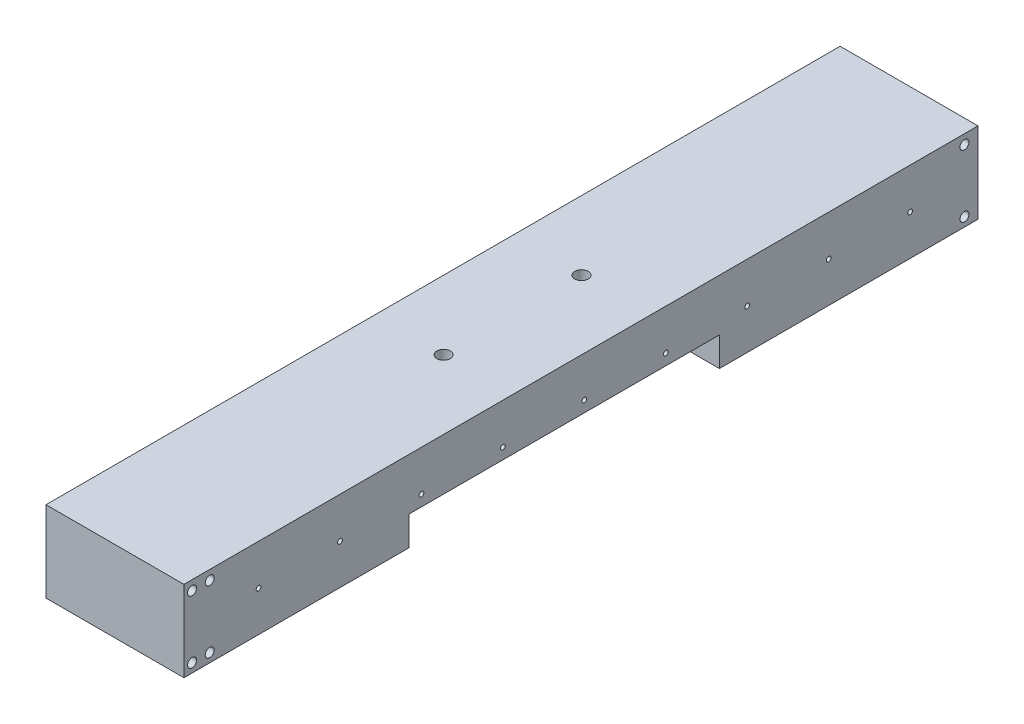
SolidWorks part; units mm, degrees
ref_plane "Front" through (0, 0, 0) normal (0, 0, 1) x (1, 0, 0)
ref_plane "Top" through (0, 0, 0) normal (0, 1, 0) x (1, 0, 0)
ref_plane "Right" through (0, 0, 0) normal (1, 0, 0) x (0, 0, -1)
sketch "Sketch1" plane through (0, 0, 0) normal (0, 0, 1) x (1, 0, 0)
  line L1 (0, 0) -> (101.6, 0)
  line L2 (0, 0) -> (0, 59.6)
  line L3 (0, 59.6) -> (101.6, 59.6)
  line L4 (101.6, 0) -> (101.6, 59.6)
  dimension "D1" = 59.6
  dimension "D2" = 101.6
extrude "Boss-Extrude1" add sketch "Sketch1" along normal blind 585.0001
sketch "Sketch2" plane through (0, 0, 0) normal (-1, 0, 0) x (0, 0, 1)
  line L0 (190.5, 0) -> (190.5, 21.5)
  line L1 (585.0001, 0) -> (0, 0) construction
  line L2 (190.5, 21.5) -> (419.1, 21.5)
  line L3 (419.1, 21.5) -> (419.1, 0)
  line L4 (419.1, 0) -> (190.5, 0)
  line L5 (0, 59.6) -> (0, 0) construction
  dimension "D1" = 190.5
  dimension "D2" = 21.5
  dimension "D3" = 228.6
extrude "Cut-Extrude1" cut sketch "Sketch2" against normal through all
sketch "Sketch5" plane through (0, 0, 0) normal (-1, 0, 0) x (0, 0, 1)
  arc A0 (6.7, 6.6) -> (13.3, 6.6) centre (10, 6.6) ccw construction
  arc A1 (13.3, 6.6) -> (6.7, 6.6) centre (10, 6.6) ccw construction
  arc A2 (6.7, 52.6) -> (13.3, 52.6) centre (10, 52.6) ccw construction
  arc A3 (13.3, 52.6) -> (6.7, 52.6) centre (10, 52.6) ccw construction
  arc A4 (6.7, 6.6) -> (13.3, 6.6) centre (10, 6.6) ccw
  arc A5 (13.3, 6.6) -> (6.7, 6.6) centre (10, 6.6) ccw
  arc A6 (6.7, 52.6) -> (13.3, 52.6) centre (10, 52.6) ccw
  arc A7 (13.3, 52.6) -> (6.7, 52.6) centre (10, 52.6) ccw
  arc A8 (170, 31.35) -> (170, 27.85) centre (170, 29.6) ccw construction
  arc A9 (170, 27.85) -> (170, 31.35) centre (170, 29.6) ccw construction
  arc A10 (110, 27.85) -> (110, 31.35) centre (110, 29.6) ccw construction
  arc A11 (110, 31.35) -> (110, 27.85) centre (110, 29.6) ccw construction
  arc A12 (50, 27.85) -> (50, 31.35) centre (50, 29.6) ccw construction
  arc A13 (50, 31.35) -> (50, 27.85) centre (50, 29.6) ccw construction
  arc A14 (170, 31.35) -> (170, 27.85) centre (170, 29.6) ccw
  arc A15 (170, 27.85) -> (170, 31.35) centre (170, 29.6) ccw
  arc A16 (110, 27.85) -> (110, 31.35) centre (110, 29.6) ccw
  arc A17 (110, 31.35) -> (110, 27.85) centre (110, 29.6) ccw
  arc A18 (50, 27.85) -> (50, 31.35) centre (50, 29.6) ccw
  arc A19 (50, 31.35) -> (50, 27.85) centre (50, 29.6) ccw
  arc A20 (530, 27.85) -> (530, 31.35) centre (530, 29.6) ccw construction
  arc A21 (530, 31.35) -> (530, 27.85) centre (530, 29.6) ccw construction
  arc A22 (470, 27.85) -> (470, 31.35) centre (470, 29.6) ccw construction
  arc A23 (470, 31.35) -> (470, 27.85) centre (470, 29.6) ccw construction
  arc A24 (410, 27.85) -> (410, 31.35) centre (410, 29.6) ccw construction
  arc A25 (410, 31.35) -> (410, 27.85) centre (410, 29.6) ccw construction
  arc A26 (350, 27.85) -> (350, 31.35) centre (350, 29.6) ccw construction
  arc A27 (350, 31.35) -> (350, 27.85) centre (350, 29.6) ccw construction
  arc A28 (290, 27.85) -> (290, 31.35) centre (290, 29.6) ccw construction
  arc A29 (290, 31.35) -> (290, 27.85) centre (290, 29.6) ccw construction
  arc A30 (230, 27.85) -> (230, 31.35) centre (230, 29.6) ccw construction
  arc A31 (230, 31.35) -> (230, 27.85) centre (230, 29.6) ccw construction
  arc A32 (530, 27.85) -> (530, 31.35) centre (530, 29.6) ccw
  arc A33 (530, 31.35) -> (530, 27.85) centre (530, 29.6) ccw
  arc A34 (470, 27.85) -> (470, 31.35) centre (470, 29.6) ccw
  arc A35 (470, 31.35) -> (470, 27.85) centre (470, 29.6) ccw
  arc A36 (410, 27.85) -> (410, 31.35) centre (410, 29.6) ccw
  arc A37 (410, 31.35) -> (410, 27.85) centre (410, 29.6) ccw
  arc A38 (350, 27.85) -> (350, 31.35) centre (350, 29.6) ccw
  arc A39 (350, 31.35) -> (350, 27.85) centre (350, 29.6) ccw
  arc A40 (290, 27.85) -> (290, 31.35) centre (290, 29.6) ccw
  arc A41 (290, 31.35) -> (290, 27.85) centre (290, 29.6) ccw
  arc A42 (230, 27.85) -> (230, 31.35) centre (230, 29.6) ccw
  arc A43 (230, 31.35) -> (230, 27.85) centre (230, 29.6) ccw
  arc A44 (582.3, 6.6) -> (575.7, 6.6) centre (579, 6.6) ccw construction
  arc A45 (575.7, 6.6) -> (582.3, 6.6) centre (579, 6.6) ccw construction
  arc A46 (562.7, 6.6) -> (569.3, 6.6) centre (566, 6.6) ccw construction
  arc A47 (569.3, 6.6) -> (562.7, 6.6) centre (566, 6.6) ccw construction
  arc A48 (575.7, 52.6) -> (582.3, 52.6) centre (579, 52.6) ccw construction
  arc A49 (582.3, 52.6) -> (575.7, 52.6) centre (579, 52.6) ccw construction
  arc A50 (562.7, 52.6) -> (569.3, 52.6) centre (566, 52.6) ccw construction
  arc A51 (569.3, 52.6) -> (562.7, 52.6) centre (566, 52.6) ccw construction
  arc A52 (582.3, 6.6) -> (575.7, 6.6) centre (579, 6.6) ccw
  arc A53 (575.7, 6.6) -> (582.3, 6.6) centre (579, 6.6) ccw
  arc A54 (562.7, 6.6) -> (569.3, 6.6) centre (566, 6.6) ccw
  arc A55 (569.3, 6.6) -> (562.7, 6.6) centre (566, 6.6) ccw
  arc A56 (575.7, 52.6) -> (582.3, 52.6) centre (579, 52.6) ccw
  arc A57 (582.3, 52.6) -> (575.7, 52.6) centre (579, 52.6) ccw
  arc A58 (562.7, 52.6) -> (569.3, 52.6) centre (566, 52.6) ccw
  arc A59 (569.3, 52.6) -> (562.7, 52.6) centre (566, 52.6) ccw
extrude "Cut-Extrude4" cut sketch "Sketch5" along normal blind 6.35 from surface contours A32 A33 | A34 A35 | A36 A37 | A38 A39 | A40 A41 | A42 A43 | A15 A14 | A16 A17 | A18 A19 starting at face at (101.6, 20.275, 298.65)
extrude "Cut-Extrude5" cut sketch "Sketch5<3>" along normal blind 25.4 from surface contours A54 A55 | A52 A53 | A56 A57 | A58 A59 | A4 A5 | A6 A7 region at (0, 6.6, 10) region at (0, 52.6, 10) region at (0, 6.6, 579) region at (0, 6.6, 566) region at (0, 52.6, 579) region at (0, 52.6, 566) starting at face at (101.6, 29.6, 531.75)
sketch "Sketch5<3>" plane through (0, 0, 0) normal (-1, 0, 0) x (0, 0, 1) same geometry as "Sketch5"
sketch "Sketch6" plane through (0, 21.5, 0) normal (0, -1, 0) x (1, 0, 0)
  circle A0 centre (50.8, 342.9) radius 4.9344 construction
  circle A1 centre (50.8, 241.3) radius 4.9344 construction
  circle A2 centre (50.8, 342.9) radius 4.9344
  circle A3 centre (50.8, 241.3) radius 4.9344
extrude "Cut-Extrude6" cut sketch "Sketch6" against normal through all
